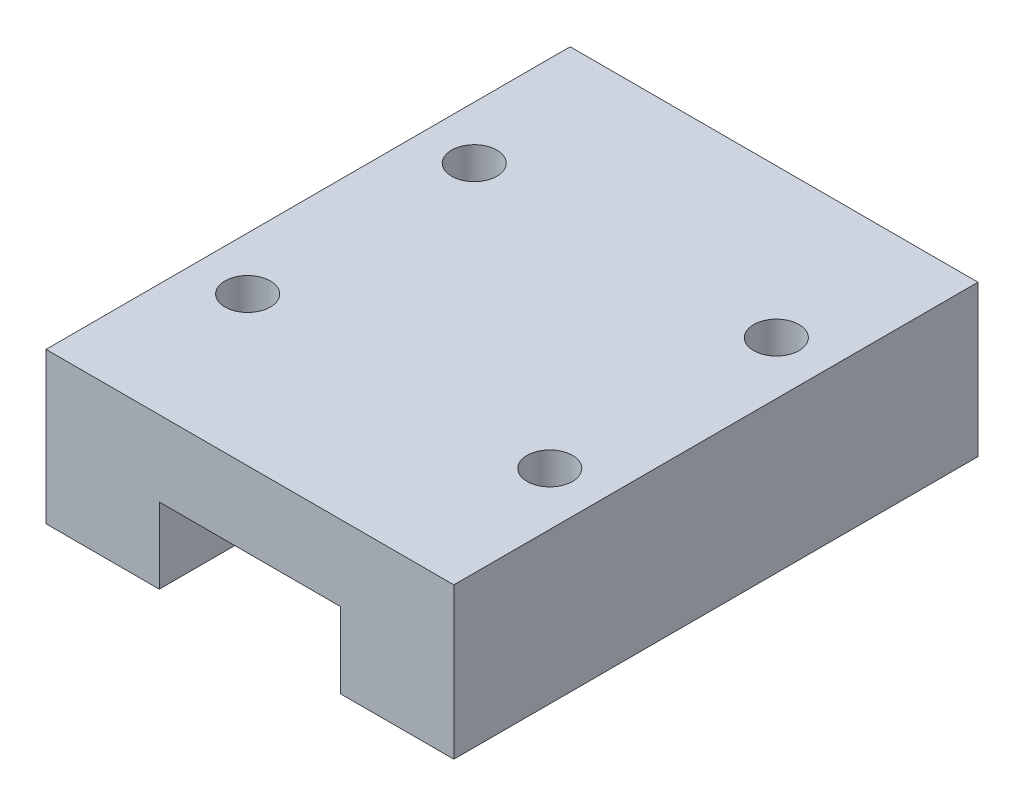
SolidWorks part; units mm, degrees
ref_plane "前视基准面" through (0, 0, 0) normal (0, 0, 1) x (1, 0, 0)
ref_plane "上视基准面" through (0, 0, 0) normal (0, 1, 0) x (1, 0, 0)
ref_plane "右视基准面" through (0, 0, 0) normal (1, 0, 0) x (0, 0, -1)
sketch "草图2" plane through (0, 0, 0) normal (0, 0, 1) x (1, 0, 0)
  line L1 (13.5, -5) -> (-13.5, -5)
  line L2 (13.5, -5) -> (13.5, 5)
  line L3 (13.5, 5) -> (-13.5, 5)
  line L4 (-13.5, -5) -> (-13.5, 5)
  line L5 (13.5, -5) -> (-13.5, 5) construction
  line L6 (13.5, 5) -> (-13.5, -5) construction
  line L7 (-6, 0) -> (6, 0)
  line L8 (-6, 0) -> (-6, -5)
  line L9 (-6, -5) -> (6, -5)
  line L10 (6, 0) -> (6, -5)
  line L11 (-6, 0) -> (6, -5) construction
  line L12 (-6, -5) -> (6, 0) construction
  point P0 (0, 0)
  point P6 (0, -2.5)
  point P11 (0, 0)
  dimension "D1" = 27
  dimension "D2" = 10
  dimension "D3" = 12
  dimension "D4" = 5
extrude "凸台-拉伸1" add sketch "草图2" along normal blind 34.7 contours L7 L10 L1 L2 L3 L4 L8 region at (0, 0.7143, 0)
sketch "草图3" plane through (0, 5, 0) normal (0, 1, 0) x (1, 0, 0)
  line L0 (-13.5, 0) -> (13.5, -34.7) construction
  line L2 (-10, -24.85) -> (10, -24.85) construction
  line L3 (-10, -24.85) -> (-10, -9.85) construction
  line L4 (-10, -9.85) -> (10, -9.85) construction
  line L5 (10, -24.85) -> (10, -9.85) construction
  line L6 (-10, -24.85) -> (10, -9.85) construction
  line L7 (-10, -9.85) -> (10, -24.85) construction
  circle A0 centre (-10, -9.85) radius 1.5
  circle A1 centre (10, -9.85) radius 1.5
  circle A2 centre (10, -24.85) radius 1.5
  circle A3 centre (-10, -24.85) radius 1.5
  point P4 (0, -17.35)
  dimension "D3" = 3
  dimension "D4" = 3
  dimension "D5" = 3
  dimension "D6" = 3
  dimension "D1" = 15
  dimension "D2" = 20
extrude "切除-拉伸1" cut sketch "草图3" against normal blind 3.5
